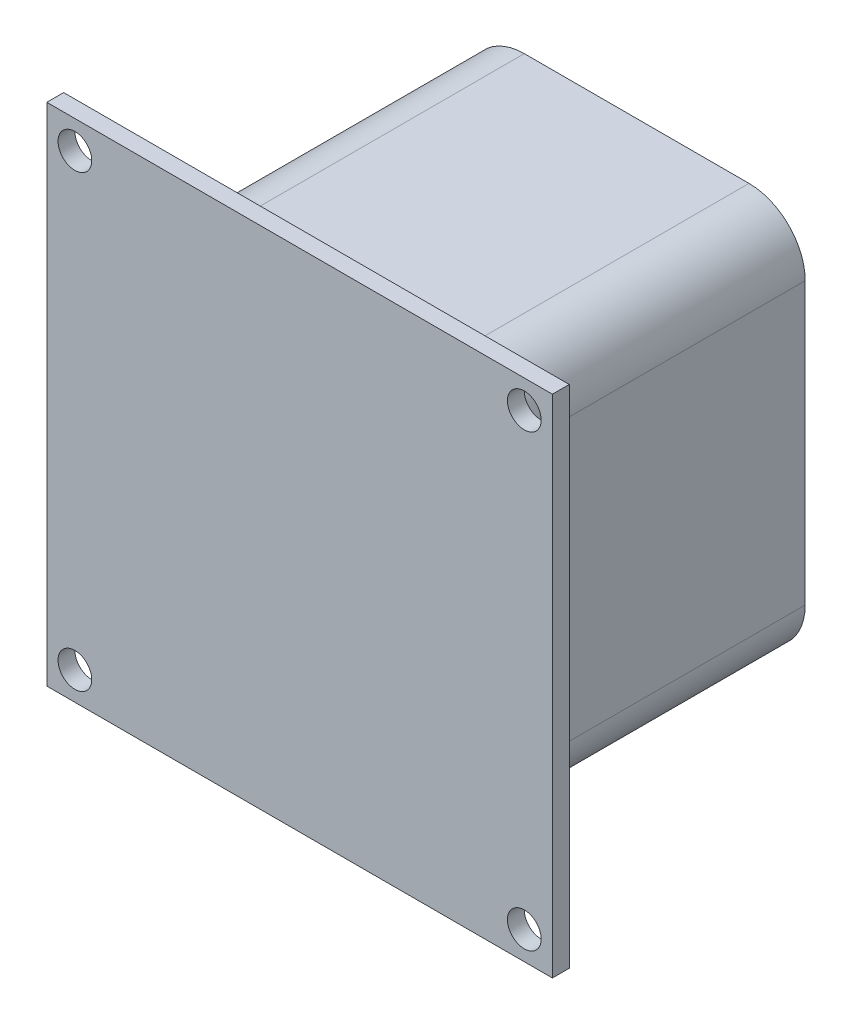
SolidWorks part; units mm, degrees
ref_plane "Front Plane" through (0, 0, 0) normal (0, 0, 1) x (1, 0, 0)
ref_plane "Top Plane" through (0, 0, 0) normal (0, 1, 0) x (1, 0, 0)
ref_plane "Right Plane" through (0, 0, 0) normal (1, 0, 0) x (0, 0, -1)
sketch "Sketch1" plane through (0, 0, 0) normal (0, 0, 1) x (1, 0, 0)
  line L1 (-30, -35) -> (30, -35)
  line L2 (-30, -35) -> (-30, 35)
  line L3 (-30, 35) -> (30, 35)
  line L4 (30, -35) -> (30, 35)
  line L5 (-30, -35) -> (30, 35) construction
  line L6 (-30, 35) -> (30, -35) construction
  line L7 (20, -30) -> (-20, -30)
  line L8 (25, -25) -> (25, 25)
  line L9 (20, 30) -> (-20, 30)
  line L10 (-25, -25) -> (-25, 25)
  line L11 (25, -30) -> (-25, 30) construction
  line L12 (25, 30) -> (-25, -30) construction
  arc A0 (-20, -30) -> (-25, -25) centre (-20, -25) cw
  arc A1 (20, -30) -> (25, -25) centre (20, -25) ccw
  arc A2 (25, 25) -> (20, 30) centre (20, 25) ccw
  arc A3 (-20, 30) -> (-25, 25) centre (-20, 25) ccw
  point P0 (0, 0)
  point P6 (0, 0)
  dimension "D3" = 5
  dimension "D1" = 70
  dimension "D2" = 60
  dimension "D4" = 60
  dimension "D5" = 50
extrude "Boss-Extrude1" add sketch "Sketch1" along normal blind 60
sketch "Sketch2" plane through (0, 0, 0) normal (0, 0, -1) x (-1, 0, 0)
  line L0 (0, 5) -> (0, -30) construction
  line L1 (-16.65, 2) -> (-10.65, 2)
  line L2 (-10.65, 2) -> (-10.65, -25)
  line L3 (-10.65, -25) -> (10.65, -25)
  line L4 (10.65, -25) -> (10.65, 2)
  line L5 (10.65, 2) -> (16.65, 2)
  line L6 (16.65, 2) -> (16.65, -25)
  line L7 (-16.65, 2) -> (-16.65, -25)
  line L8 (0, 5) -> (13.5, 5) construction
  line L9 (13.5, 5) -> (13.5, -2) construction
  line L10 (13.5, -2) -> (13.5, -10) construction
  line L11 (13.5, -10) -> (13.5, -18) construction
  line L12 (-20, -30) -> (20, -30)
  line L13 (-16.65, -25) -> (-25, -25)
  line L14 (16.65, -25) -> (25, -25)
  line L15 (20, -30) -> (-20, -30) construction
  circle A0 centre (0, 5) radius 11 construction
  circle A1 centre (13.5, -2) radius 1.25
  arc A2 (-25, -25) -> (-20, -30) centre (-20, -25) ccw
  circle A3 centre (13.5, -10) radius 1.25
  circle A4 centre (13.5, -18) radius 1.25
  circle A5 centre (-13.5, -2) radius 1.25
  circle A6 centre (-13.5, -10) radius 1.25
  circle A7 centre (-13.5, -18) radius 1.25
  arc A8 (20, -30) -> (25, -25) centre (20, -25) ccw
  arc A9 (-25, -25) -> (-20, -30) centre (-20, -25) ccw construction
  point P6 (0, -25)
  point P31 (-14.5247, -3.5147)
  point P34 (0, -30)
  point P35 (0, 0)
  point P36 (-20, -30)
  point P40 (-25, -25)
  dimension "D1" = 22
  dimension "D5" = 2.5
  dimension "D2" = 21.3
  dimension "D3" = 13.5
  dimension "D4" = 7
  dimension "D6" = 8
  dimension "D7" = 8
  dimension "D8" = 6
  dimension "D9" = 3
  dimension "D10" = 5
  dimension "D11" = 30
extrude "Boss-Extrude2" add sketch "Sketch2" against normal blind 3.5
sketch "Sketch4" plane through (0, -35, 0) normal (0, -1, 0) x (1, 0, 0)
  line L0 (-30, 60) -> (30, 60) construction
  line L1 (15, 60) -> (-15, 60)
  line L2 (15, 60) -> (15, 48)
  line L3 (15, 48) -> (-15, 48)
  line L4 (-15, 60) -> (-15, 48)
  line L5 (0, 0) -> (0, 60) construction
  line L6 (-30, 0) -> (30, 0) construction
  point P10 (0, 60)
  dimension "D1" = 30
  dimension "D2" = 12
extrude "Cut-Extrude1" cut sketch "Sketch4" against normal up to surface (5 mm away) up to face at (0, -30, 31.75)
sketch "Sketch5" plane through (0, 0, 0) normal (0, 0, -1) x (-1, 0, 0)
  circle A0 centre (-13.5, -2) radius 2.25
  circle A1 centre (-13.5, -10) radius 2.25
  circle A2 centre (-13.5, -18) radius 2.25
  circle A3 centre (13.5, -18) radius 2.25
  circle A4 centre (13.5, -10) radius 2.25
  circle A5 centre (13.5, -2) radius 2.25
  dimension "D1" = 4.5
extrude "Cut-Extrude2" cut sketch "Sketch5" against normal blind 3
sketch "Sketch6" plane through (0, 0, 60) normal (0, 0, 1) x (1, 0, 0)
  line L1 (-45, 45) -> (45, 45)
  line L2 (-45, 45) -> (-45, -45)
  line L3 (-45, -45) -> (45, -45)
  line L4 (45, 45) -> (45, -45)
  line L5 (-45, 45) -> (45, -45) construction
  line L6 (-45, -45) -> (45, 45) construction
  line L7 (40, 40) -> (-40, 40) construction
  line L8 (40, 40) -> (40, -40) construction
  line L9 (40, -40) -> (-40, -40) construction
  line L10 (-40, 40) -> (-40, -40) construction
  line L11 (40, 40) -> (-40, -40) construction
  line L12 (40, -40) -> (-40, 40) construction
  circle A0 centre (40, 40) radius 3
  circle A1 centre (-40, 40) radius 3
  circle A2 centre (-40, -40) radius 3
  circle A3 centre (40, -40) radius 3
  point P0 (0, 0)
  point P6 (0, 0)
  dimension "D5" = 6
  dimension "D1" = 90
  dimension "D2" = 90
  dimension "D3" = 80
  dimension "D4" = 80
extrude "Boss-Extrude3" add sketch "Sketch6" against normal blind 3
fillet "Fillet1" radius 10 4 edges at (-30, -35, 28.5) (30, -35, 28.5) (-30, 35, 28.5) (30, 35, 28.5)
